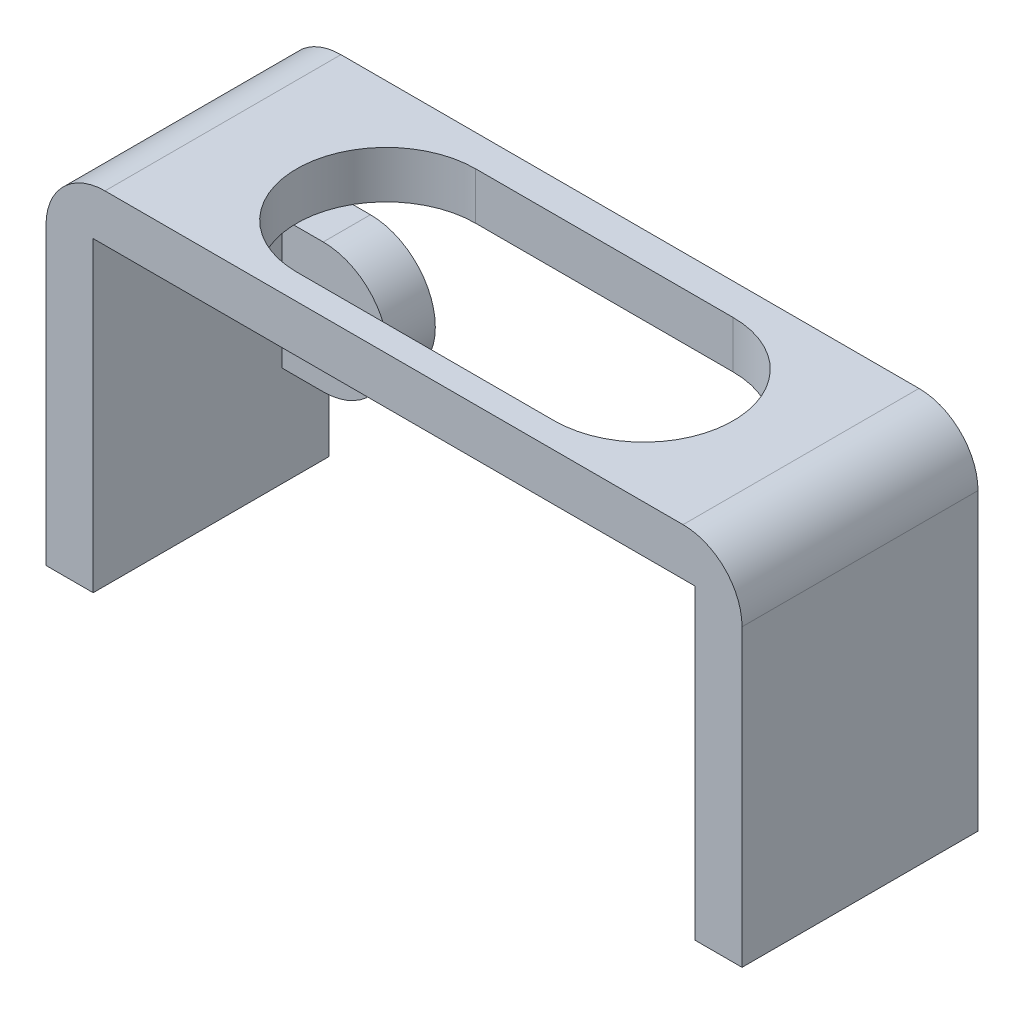
SolidWorks part; units mm, degrees
ref_plane "前视基准面" through (0, 0, 0) normal (0, 0, 1) x (1, 0, 0)
ref_plane "上视基准面" through (0, 0, 0) normal (0, 1, 0) x (1, 0, 0)
ref_plane "右视基准面" through (0, 0, 0) normal (1, 0, 0) x (0, 0, -1)
other "Configuration Table"
sketch "草图1" plane through (0, 0, 0) normal (0, 0, 1) x (1, 0, 0)
  line L0 (0, 0) -> (0, 30)
  line L1 (0, 30) -> (59, 30)
  line L2 (59, 30) -> (59, 0)
  line L3 (2, 0) -> (2, 28)
  line L4 (2, 28) -> (57, 28)
  line L5 (57, 28) -> (57, 0)
  line L6 (0, 0) -> (2, 0)
  line L7 (57, 0) -> (59, 0)
  line L8 (2, 14) -> (6, 14) construction
  line L9 (29.5, 28) -> (29.5, 0) construction
  line L11 (7.5, 19.5) -> (2, 19.5)
  line L12 (7.5, 8.5) -> (2, 8.5)
  line L15 (51.5, 8.5) -> (57, 8.5)
  line L16 (51.5, 19.5) -> (57, 19.5)
  line L19 (2, 19.5) -> (2, 8.5)
  line L22 (57, 19.5) -> (57, 8.5)
  circle A0 centre (7.5, 14) radius 1.5
  arc A2 (7.5, 8.5) -> (7.5, 19.5) centre (7.5, 14) ccw
  circle A4 centre (7.5, 14) radius 5.5 construction
  circle A6 centre (51.5, 14) radius 1.5
  arc A7 (51.5, 8.5) -> (51.5, 19.5) centre (51.5, 14) cw
  dimension "D5" = 3
  dimension "D1" = 30
  dimension "D2" = 59
  dimension "D3" = 2
  dimension "D6" = 4
  dimension "D9" = 4
extrude "凸台-拉伸1" add sketch "草图1" along normal blind 4 contours L12 A2 L11 L3 A0 | L4 | L4 | A7 L15 L5 L16 A6 region at (2.1556, 14, 0) region at (54.25, 8.6556, 0)
extrude "凸台-拉伸2" add sketch "草图1<3>" along normal blind 20 contours L5 L7 L2 L1 L0 L6 L3 L4 region at (0.6619, 15, 0)
sketch "草图1<3>" plane through (0, 0, 0) normal (0, 0, 1) x (1, 0, 0) same geometry as "草图1"
fillet "圆角2" radius 5 2 edges at (59, 30, 10) (0, 30, 10)
sketch "草图4" plane through (0, 28, 0) normal (0, -1, 0) x (1, 0, 0)
  line L4 (2, 0) -> (57, 0)
  line L5 (57, 0) -> (57, 20)
  line L6 (57, 20) -> (2, 20)
  line L7 (2, 20) -> (2, 0)
  line L8 (2, 0) -> (57, 0)
  line L9 (57, 0) -> (57, 20)
  line L10 (57, 20) -> (2, 20)
  line L11 (2, 20) -> (2, 0)
  dimension "D1" = 0
extrude "凸台-拉伸3" add sketch "草图4" along normal blind 2
sketch "草图5" plane through (2, 0, 0) normal (1, 0, 0) x (0, 0, -1)
  line L8 (0, 19.5) -> (0, 26)
  line L9 (0, 26) -> (-20, 26)
  line L10 (-20, 26) -> (-20, 0)
  line L11 (-20, 0) -> (0, 0)
  line L12 (0, 0) -> (0, 8.5)
  line L13 (0, 8.5) -> (-4, 8.5)
  line L14 (-4, 8.5) -> (-4, 19.5)
  line L15 (0, 8.5) -> (-4, 8.5)
  line L16 (0, 19.5) -> (0, 26)
  line L17 (0, 26) -> (-20, 26)
  line L18 (-20, 26) -> (-20, 0)
  line L19 (-20, 0) -> (0, 0)
  line L20 (0, 0) -> (0, 8.5)
  line L22 (-4, 8.5) -> (-4, 19.5)
  line L24 (-4, 19.5) -> (0, 19.5)
  line L25 (-4, 19.5) -> (0, 19.5)
  dimension "D1" = 0
extrude "凸台-拉伸4" add sketch "草图5" along normal blind 2
sketch "草图7" plane through (57, 0, 0) normal (-1, 0, 0) x (0, 0, 1)
  line L8 (20, 0) -> (20, 26)
  line L9 (20, 26) -> (0, 26)
  line L10 (0, 26) -> (0, 19.5)
  line L11 (0, 19.5) -> (4, 19.5)
  line L12 (4, 19.5) -> (4, 8.5)
  line L13 (0, 19.5) -> (4, 19.5)
  line L14 (0, 8.5) -> (0, 0)
  line L15 (0, 0) -> (20, 0)
  line L16 (20, 0) -> (20, 26)
  line L17 (20, 26) -> (0, 26)
  line L18 (0, 26) -> (0, 19.5)
  line L20 (4, 19.5) -> (4, 8.5)
  line L22 (0, 8.5) -> (0, 0)
  line L23 (0, 0) -> (20, 0)
  line L24 (4, 8.5) -> (0, 8.5)
  line L25 (4, 8.5) -> (0, 8.5)
  dimension "D1" = 0
extrude "凸台-拉伸5" add sketch "草图7" along normal blind 2
sketch "草图8" plane through (0, 30, 0) normal (0, 1, 0) x (1, 0, 0)
  line L0 (40.92, -10.2509) -> (19.0826, -10.2509) construction
  line L1 (40.92, -17.8329) -> (19.0826, -17.8329)
  line L2 (40.92, -2.669) -> (19.0826, -2.669)
  line L3 (29.5, -20) -> (29.5, 0) construction
  line L4 (5, -20) -> (54, -20) construction
  line L5 (5, 0) -> (54, 0) construction
  arc A0 (40.92, -17.8329) -> (40.92, -2.669) centre (40.92, -10.2509) ccw
  arc A1 (19.0826, -2.669) -> (19.0826, -17.8329) centre (19.0826, -10.2509) ccw
  point P2 (30.0013, -10.2509)
  dimension "D1" = 11.42
extrude "切除-拉伸2" cut sketch "草图8" against normal blind 7
